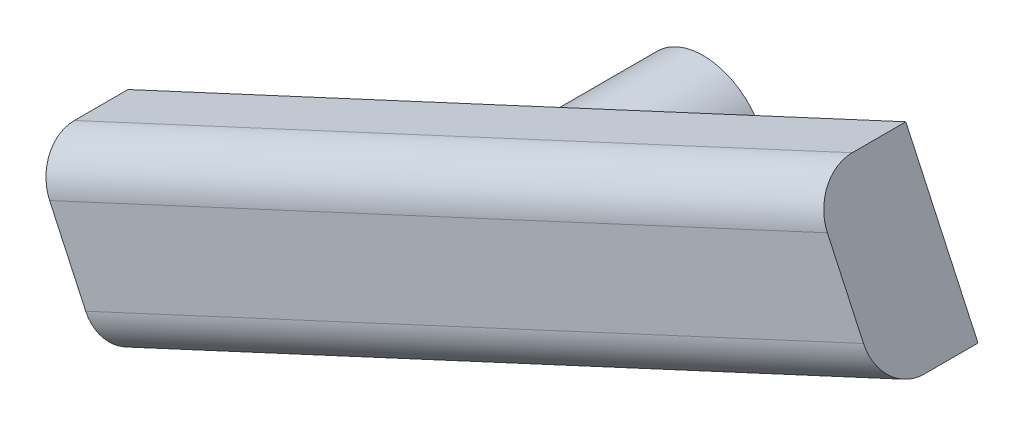
SolidWorks part; units mm, degrees
material "NEOPRENO"
ref_plane "Alzado" through (0, 0, 0) normal (0, 0, 1) x (1, 0, 0)
ref_plane "Planta" through (0, 0, 0) normal (0, 1, 0) x (1, 0, 0)
ref_plane "Vista lateral" through (0, 0, 0) normal (1, 0, 0) x (0, 0, -1)
sketch3d "Sk_Vastago"
  line L0 (455.3416, 345.3626, -22) -> (455.3416, 345.3626, -15)
sweep "Vastago" add path "Sk_Vastago" circular profile diameter 6 parameters "D3"=6
sketch "Sk_Goma" plane through (0, 0, 0) normal (0, 0, 1) x (1, 0, 0)
  line L0 (438.8839, 333.315) -> (435.5162, 340.5716)
  line L1 (435.5162, 340.5716) -> (471.7992, 357.4103)
  line L2 (471.7992, 357.4103) -> (475.1669, 350.1537)
  line L3 (475.1669, 350.1537) -> (438.8839, 333.315)
extrude "Goma" add sketch "Sk_Goma" along normal blind 4.5 from offset 15 offset against normal yes
fillet "Redondeo1" radius 2 2 edges at (457.0254, 341.7343, -10.5) (453.6577, 348.9909, -10.5)
